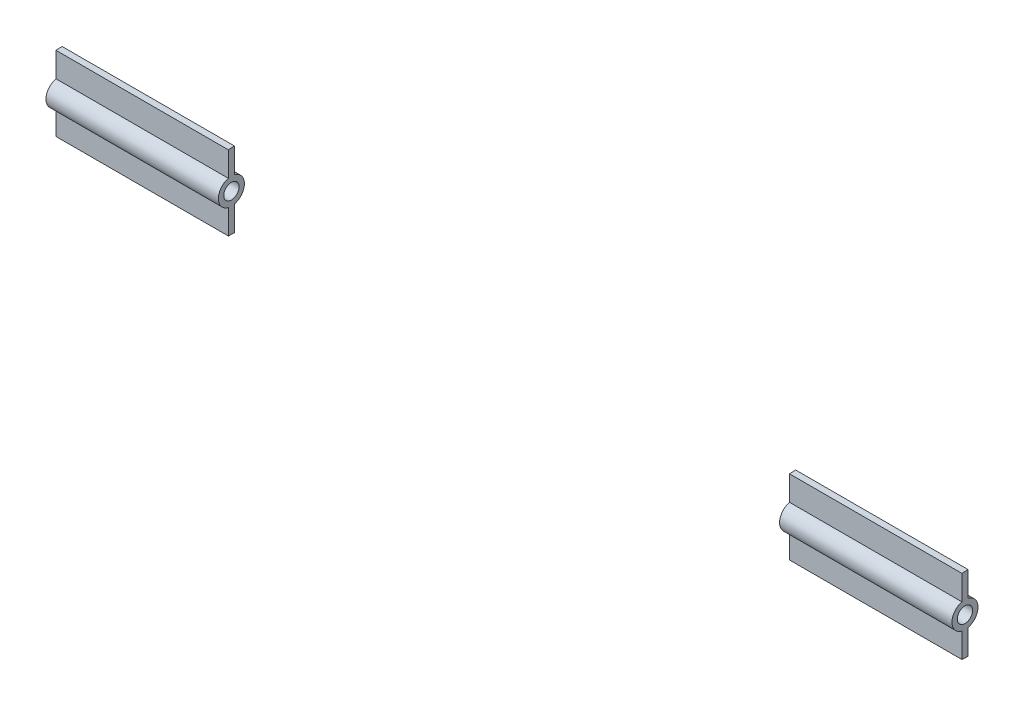
SolidWorks part; units mm, degrees
material "ABS"
ref_plane "Front Plane" through (0, 0, 0) normal (0, 0, 1) x (1, 0, 0)
ref_plane "Top Plane" through (0, 0, 0) normal (0, 1, 0) x (1, 0, 0)
ref_plane "Right Plane" through (0, 0, 0) normal (1, 0, 0) x (0, 0, -1)
body saved out of another part "Stock-V-tail-1" rebuild error yes
ref_plane "Plane1" through (237.5, 0, 0) normal (-1, 0, 0) x (0, 0, 1)
sketch "Sketch1" plane through (237.5, 0, 0) normal (-1, 0, 0) x (0, 0, 1)
  arc A1 (136.0381, 9.253) -> (136.0381, -9.253) centre (141.8338, 0) ccw
  arc A2 (136.0381, 9.253) -> (136.0381, -9.253) centre (141.8338, 0) ccw
  circle A5 centre (62, 0) radius 9 construction
  circle A6 centre (62, 0) radius 9
  spline S0 degree 3 poles (1848.5448, -5455.4948) (1254.8548, 370.5463) (691.9533, 13.7835) (107.9109, -10.5652) (94.6227, -10.9527) (84.1989, -11.1308) (76.6156, -11.194) (69.2347, -11.1852) (62.0877, -11.0901) (55.2058, -10.9234) (48.6191, -10.6715) (42.3552, -10.3437) (36.4402, -9.9323) (30.8991, -9.4444) (25.7573, -8.8756) (21.0365, -8.2367) (16.7549, -7.5443) (12.9305, -6.8014) (9.5757, -6.0106) (6.7064, -5.1453) (4.3287, -4.1895) (2.4645, -3.1349) (1.1239, -2.0336) (0.2866, -1.0243) (-0.1173, 0) (0.2866, 1.0243) (1.1239, 2.0336) (2.4645, 3.1349) (4.3287, 4.1895) (6.7064, 5.1453) (9.5757, 6.0106) (12.9305, 6.8014) (16.7549, 7.5443) (21.0365, 8.2367) (25.7573, 8.8756) (30.8991, 9.4444) (36.4402, 9.9323) (42.3552, 10.3437) (48.6191, 10.6715) (55.2058, 10.9234) (62.0877, 11.0901) (69.2347, 11.1852) (76.6156, 11.194) (84.1989, 11.1308) (94.6227, 10.9527) (107.9109, 10.5652) (691.9613, -13.7839) (1254.8704, -370.5562) (1848.5696, 5455.7381) knots -6.166881 -6.166881 -6.166881 -6.166881 0.043484 0.10192 0.159336 0.187352 0.214748 0.241409 0.267232 0.292102 0.315909 0.338567 0.359984 0.380076 0.398764 0.415965 0.431629 0.445697 0.45812 0.468916 0.478106 0.485795 0.492019 0.496734 0.5 0.503266 0.507981 0.514205 0.521894 0.531084 0.54188 0.554303 0.568371 0.584035 0.601236 0.619924 0.640016 0.661433 0.684091 0.707898 0.732768 0.758591 0.785252 0.812648 0.840664 0.89808 0.956516 7.166968 7.166968 7.166968 7.166968 only from (136.0381, -9.253) to (136.0381, 9.253)
  spline S1 degree 3 poles (136.0381, -9.253) (132.0261, -9.4717) (122.621, -9.9519) (107.9109, -10.5652) (94.6227, -10.9527) (84.1989, -11.1308) (76.6156, -11.194) (69.2347, -11.1852) (62.0877, -11.0901) (55.2058, -10.9234) (48.6191, -10.6715) (42.3552, -10.3437) (36.4402, -9.9323) (30.8991, -9.4444) (25.7573, -8.8756) (21.0365, -8.2367) (16.7549, -7.5443) (12.9305, -6.8014) (9.5757, -6.0106) (6.7064, -5.1453) (4.3287, -4.1895) (2.4645, -3.1349) (1.1239, -2.0336) (0.2866, -1.0243) (-0.1173, 0) (0.2866, 1.0243) (1.1239, 2.0336) (2.4645, 3.1349) (4.3287, 4.1895) (6.7064, 5.1453) (9.5757, 6.0106) (12.9305, 6.8014) (16.7549, 7.5443) (21.0365, 8.2367) (25.7573, 8.8756) (30.8991, 9.4444) (36.4402, 9.9323) (42.3552, 10.3437) (48.6191, 10.6715) (55.2058, 10.9234) (62.0877, 11.0901) (69.2347, 11.1852) (76.6156, 11.194) (84.1989, 11.1308) (94.6227, 10.9527) (107.9109, 10.5652) (122.621, 9.9519) (132.0261, 9.4717) (136.0381, 9.253) knots 0 0 0 0 0.043484 0.10192 0.159336 0.187352 0.214748 0.241409 0.267232 0.292102 0.315909 0.338567 0.359984 0.380076 0.398764 0.415965 0.431629 0.445697 0.45812 0.468916 0.478106 0.485795 0.492019 0.496734 0.5 0.503266 0.507981 0.514205 0.521894 0.531084 0.54188 0.554303 0.568371 0.584035 0.601236 0.619924 0.640016 0.661433 0.684091 0.707898 0.732768 0.758591 0.785252 0.812648 0.840664 0.89808 0.956516 1 1 1 1
extrude "Boss-Extrude1" add sketch "Sketch1" along normal up to surface (1 mm away) rebuild error yes
sketch "Sketch3" plane through (236.5, 0, 0) normal (-1, 0, 0) x (0, 0, 1)
  line L0 (62, 0) -> (117, 0) construction
  line L1 (116.2, 9.8114) -> (116.2, 3.3045)
  line L2 (117.8, 9.7438) -> (117.8, 3.3045)
  line L3 (117, 9.7778) -> (117, -9.7778) construction
  line L4 (116.2, -9.8114) -> (116.2, -3.3045)
  line L5 (117.8, -9.7438) -> (117.8, -3.3045)
  line L6 (116.2, 9.8114) -> (117.8, 9.7438)
  line L7 (116.2, -9.8114) -> (117.8, -9.7438)
  circle A0 centre (62, 0) radius 9 construction
  circle A1 centre (62, 0) radius 9 construction
  circle A2 centre (117, 0) radius 2
  arc A3 (116.2, 3.3045) -> (116.2, -3.3045) centre (117, 0) ccw
  arc A4 (117.8, -3.3045) -> (117.8, 3.3045) centre (117, 0) ccw
  spline S0 degree 3 poles (1848.5448, 5455.4948) (1254.8548, -370.5463) (691.9533, -13.7835) (107.9109, 10.5652) (94.6227, 10.9527) (84.1989, 11.1308) (76.6156, 11.194) (69.2347, 11.1852) (62.0877, 11.0901) (55.2058, 10.9234) (48.6191, 10.6715) (42.3552, 10.3437) (36.4402, 9.9323) (30.8991, 9.4444) (25.7573, 8.8756) (21.0365, 8.2367) (16.7549, 7.5443) (12.9305, 6.8014) (9.5757, 6.0106) (6.7064, 5.1453) (4.3287, 4.1895) (2.4645, 3.1349) (1.1239, 2.0336) (0.2866, 1.0243) (-0.1173, 0) (0.2866, -1.0243) (1.1239, -2.0336) (2.4645, -3.1349) (4.3287, -4.1895) (6.7064, -5.1453) (9.5757, -6.0106) (12.9305, -6.8014) (16.7549, -7.5443) (21.0365, -8.2367) (25.7573, -8.8756) (30.8991, -9.4444) (36.4402, -9.9323) (42.3552, -10.3437) (48.6191, -10.6715) (55.2058, -10.9234) (62.0877, -11.0901) (69.2347, -11.1852) (76.6156, -11.194) (84.1989, -11.1308) (94.6227, -10.9527) (107.9109, -10.5652) (691.9613, 13.7839) (1254.8704, 370.5562) (1848.5696, -5455.7381) knots -6.166881 -6.166881 -6.166881 -6.166881 0.043484 0.10192 0.159336 0.187352 0.214748 0.241409 0.267232 0.292102 0.315909 0.338567 0.359984 0.380076 0.398764 0.415965 0.431629 0.445697 0.45812 0.468916 0.478106 0.485795 0.492019 0.496734 0.5 0.503266 0.507981 0.514205 0.521894 0.531084 0.54188 0.554303 0.568371 0.584035 0.601236 0.619924 0.640016 0.661433 0.684091 0.707898 0.732768 0.758591 0.785252 0.812648 0.840664 0.89808 0.956516 7.166968 7.166968 7.166968 7.166968 only from (136.0381, 9.253) to (136.0381, -9.253)
  spline S1 degree 3 poles (136.0381, 9.253) (132.0261, 9.4717) (122.621, 9.9519) (107.9109, 10.5652) (94.6227, 10.9527) (84.1989, 11.1308) (76.6156, 11.194) (69.2347, 11.1852) (62.0877, 11.0901) (55.2058, 10.9234) (48.6191, 10.6715) (42.3552, 10.3437) (36.4402, 9.9323) (30.8991, 9.4444) (25.7573, 8.8756) (21.0365, 8.2367) (16.7549, 7.5443) (12.9305, 6.8014) (9.5757, 6.0106) (6.7064, 5.1453) (4.3287, 4.1895) (2.4645, 3.1349) (1.1239, 2.0336) (0.2866, 1.0243) (-0.1173, 0) (0.2866, -1.0243) (1.1239, -2.0336) (2.4645, -3.1349) (4.3287, -4.1895) (6.7064, -5.1453) (9.5757, -6.0106) (12.9305, -6.8014) (16.7549, -7.5443) (21.0365, -8.2367) (25.7573, -8.8756) (30.8991, -9.4444) (36.4402, -9.9323) (42.3552, -10.3437) (48.6191, -10.6715) (55.2058, -10.9234) (62.0877, -11.0901) (69.2347, -11.1852) (76.6156, -11.194) (84.1989, -11.1308) (94.6227, -10.9527) (107.9109, -10.5652) (122.621, -9.9519) (132.0261, -9.4717) (136.0381, -9.253) knots 0 0 0 0 0.043484 0.10192 0.159336 0.187352 0.214748 0.241409 0.267232 0.292102 0.315909 0.338567 0.359984 0.380076 0.398764 0.415965 0.431629 0.445697 0.45812 0.468916 0.478106 0.485795 0.492019 0.496734 0.5 0.503266 0.507981 0.514205 0.521894 0.531084 0.54188 0.554303 0.568371 0.584035 0.601236 0.619924 0.640016 0.661433 0.684091 0.707898 0.732768 0.758591 0.785252 0.812648 0.840664 0.89808 0.956516 1 1 1 1 construction
  spline S2 degree 1 poles (136.0163, 8.8536) (136.0163, -8.8536) knots 0 0 1 1 construction
  spline S3 degree 3 poles (136.0163, 8.8536) (130.2514, 9.1678) (124.2459, 9.4651) (118.1056, 9.7307) (117.6666, 9.7495) (117.4, 9.7609) (117.1333, 9.7722) (116.8666, 9.7835) (116.6, 9.7947) (116.3333, 9.8058) (111.2706, 10.0168) (100.5041, 10.4086) (84.0958, 10.7773) (69.6656, 10.8196) (58.1244, 10.6127) (49.4737, 10.3215) (40.8313, 9.8647) (33.6424, 9.3078) (27.907, 8.7199) (23.6162, 8.1931) (19.3389, 7.5713) (15.0835, 6.8329) (11.5652, 6.0893) (8.7915, 5.3615) (6.7466, 4.7182) (4.7593, 3.9358) (2.8953, 2.9508) (1.5069, 1.8551) (0.7638, 0.969) (0.4573, 0.3737) (0.3714, 0) (0.4573, -0.3737) (0.7638, -0.969) (1.5069, -1.8551) (2.8953, -2.9508) (4.7593, -3.9358) (6.7466, -4.7182) (8.7915, -5.3615) (11.5652, -6.0893) (15.0835, -6.8329) (19.3389, -7.5713) (23.6162, -8.1931) (27.907, -8.7199) (33.6424, -9.3078) (40.8313, -9.8647) (49.4737, -10.3215) (58.1244, -10.6127) (69.6656, -10.8196) (84.0958, -10.7773) (100.5041, -10.4086) (111.2706, -10.0168) (116.3333, -9.8058) (116.6, -9.7947) (116.8666, -9.7835) (117.1333, -9.7722) (117.4, -9.7609) (117.6666, -9.7495) (118.1056, -9.7307) (124.2459, -9.4651) (130.2514, -9.1678) (136.0163, -8.8536) knots 0 0 0 0 0.0625 0.065089 0.066534 0.067256 0.067979 0.069423 0.070146 0.070868 0.072313 0.125 0.1875 0.25 0.28125 0.3125 0.34375 0.375 0.390625 0.40625 0.421875 0.4375 0.453125 0.460938 0.46875 0.476562 0.484375 0.492188 0.496094 0.498047 0.5 0.501953 0.503906 0.507812 0.515625 0.523438 0.53125 0.539062 0.546875 0.5625 0.578125 0.59375 0.609375 0.625 0.65625 0.6875 0.71875 0.75 0.8125 0.875 0.927687 0.929132 0.929854 0.930577 0.932021 0.932744 0.933466 0.934911 0.9375 1 1 1 1 construction
  dimension "D1" = 0.4
  dimension "D2" = 55
  dimension "D3" = 4
  dimension "D4" = 6.8
  dimension "D5" = 0.8
  dimension "D6" = 0.8
extrude "Cut-Extrude1" cut sketch "Sketch3" against normal blind 44 contours A2 rebuild error yes
extrude "Boss-Extrude2" add sketch "Sketch3<3>" against normal blind 45 contours L5 A4 L2 L6 L1 A3 L4 L7 A2 region at (236.5, 9.5701, 116.9912)
sketch "Sketch3<3>" plane through (236.5, 0, 0) normal (-1, 0, 0) x (0, 0, 1) same geometry as "Sketch3"
sketch "Sketch4" plane through (473, 0, 0) normal (1, 0, 0) x (0, 0, -1)
  line L0 (-117, 9.7778) -> (-117, -9.7778) construction
  line L1 (-117.8, 9.7438) -> (-117.8, 3.3045)
  line L2 (-116.2, 9.8114) -> (-116.2, 3.3045)
  line L3 (-117.8, -9.7438) -> (-117.8, -3.3045)
  line L4 (-116.2, -9.8114) -> (-116.2, -3.3045)
  line L5 (-117.8, -9.7438) -> (-116.2, -9.8114)
  line L6 (-117.8, 9.7438) -> (-116.2, 9.8114)
  circle A0 centre (-62, 0) radius 9 construction
  circle A1 centre (-62, 0) radius 9 construction
  circle A2 centre (-117, 0) radius 2
  arc A3 (-117.8, 3.3045) -> (-117.8, -3.3045) centre (-117, 0) ccw
  arc A4 (-116.2, -3.3045) -> (-116.2, 3.3045) centre (-117, 0) ccw
  spline S0 degree 3 poles (-1848.5448, -5455.4948) (-1254.8548, 370.5463) (-691.9533, 13.7835) (-107.9109, -10.5652) (-94.6227, -10.9527) (-84.1989, -11.1308) (-76.6156, -11.194) (-69.2347, -11.1852) (-62.0877, -11.0901) (-55.2058, -10.9234) (-48.6191, -10.6715) (-42.3552, -10.3437) (-36.4402, -9.9323) (-30.8991, -9.4444) (-25.7573, -8.8756) (-21.0365, -8.2367) (-16.7549, -7.5443) (-12.9305, -6.8014) (-9.5757, -6.0106) (-6.7064, -5.1453) (-4.3287, -4.1895) (-2.4645, -3.1349) (-1.1239, -2.0336) (-0.2866, -1.0243) (0.1173, 0) (-0.2866, 1.0243) (-1.1239, 2.0336) (-2.4645, 3.1349) (-4.3287, 4.1895) (-6.7064, 5.1453) (-9.5757, 6.0106) (-12.9305, 6.8014) (-16.7549, 7.5443) (-21.0365, 8.2367) (-25.7573, 8.8756) (-30.8991, 9.4444) (-36.4402, 9.9323) (-42.3552, 10.3437) (-48.6191, 10.6715) (-55.2058, 10.9234) (-62.0877, 11.0901) (-69.2347, 11.1852) (-76.6156, 11.194) (-84.1989, 11.1308) (-94.6227, 10.9527) (-107.9109, 10.5652) (-691.9613, -13.7839) (-1254.8704, -370.5562) (-1848.5696, 5455.7381) knots -6.166881 -6.166881 -6.166881 -6.166881 0.043484 0.10192 0.159336 0.187352 0.214748 0.241409 0.267232 0.292102 0.315909 0.338567 0.359984 0.380076 0.398764 0.415965 0.431629 0.445697 0.45812 0.468916 0.478106 0.485795 0.492019 0.496734 0.5 0.503266 0.507981 0.514205 0.521894 0.531084 0.54188 0.554303 0.568371 0.584035 0.601236 0.619924 0.640016 0.661433 0.684091 0.707898 0.732768 0.758591 0.785252 0.812648 0.840664 0.89808 0.956516 7.166968 7.166968 7.166968 7.166968 only from (-136.0381, -9.253) to (-136.0381, 9.253)
  spline S1 degree 3 poles (-136.0381, -9.253) (-132.0261, -9.4717) (-122.621, -9.9519) (-107.9109, -10.5652) (-94.6227, -10.9527) (-84.1989, -11.1308) (-76.6156, -11.194) (-69.2347, -11.1852) (-62.0877, -11.0901) (-55.2058, -10.9234) (-48.6191, -10.6715) (-42.3552, -10.3437) (-36.4402, -9.9323) (-30.8991, -9.4444) (-25.7573, -8.8756) (-21.0365, -8.2367) (-16.7549, -7.5443) (-12.9305, -6.8014) (-9.5757, -6.0106) (-6.7064, -5.1453) (-4.3287, -4.1895) (-2.4645, -3.1349) (-1.1239, -2.0336) (-0.2866, -1.0243) (0.1173, 0) (-0.2866, 1.0243) (-1.1239, 2.0336) (-2.4645, 3.1349) (-4.3287, 4.1895) (-6.7064, 5.1453) (-9.5757, 6.0106) (-12.9305, 6.8014) (-16.7549, 7.5443) (-21.0365, 8.2367) (-25.7573, 8.8756) (-30.8991, 9.4444) (-36.4402, 9.9323) (-42.3552, 10.3437) (-48.6191, 10.6715) (-55.2058, 10.9234) (-62.0877, 11.0901) (-69.2347, 11.1852) (-76.6156, 11.194) (-84.1989, 11.1308) (-94.6227, 10.9527) (-107.9109, 10.5652) (-122.621, 9.9519) (-132.0261, 9.4717) (-136.0381, 9.253) knots 0 0 0 0 0.043484 0.10192 0.159336 0.187352 0.214748 0.241409 0.267232 0.292102 0.315909 0.338567 0.359984 0.380076 0.398764 0.415965 0.431629 0.445697 0.45812 0.468916 0.478106 0.485795 0.492019 0.496734 0.5 0.503266 0.507981 0.514205 0.521894 0.531084 0.54188 0.554303 0.568371 0.584035 0.601236 0.619924 0.640016 0.661433 0.684091 0.707898 0.732768 0.758591 0.785252 0.812648 0.840664 0.89808 0.956516 1 1 1 1 construction
  spline S2 degree 1 poles (-136.0163, -8.8536) (-136.0163, 8.8536) knots 0 0 1 1 construction
  spline S3 degree 3 poles (-136.0163, -8.8536) (-130.2514, -9.1678) (-124.2459, -9.4651) (-118.1056, -9.7307) (-117.6666, -9.7495) (-117.4, -9.7609) (-117.1333, -9.7722) (-116.8666, -9.7835) (-116.6, -9.7947) (-116.3333, -9.8058) (-111.2706, -10.0168) (-100.5041, -10.4086) (-84.0958, -10.7773) (-69.6656, -10.8196) (-58.1244, -10.6127) (-49.4737, -10.3215) (-40.8313, -9.8647) (-33.6424, -9.3078) (-27.907, -8.7199) (-23.6162, -8.1931) (-19.3389, -7.5713) (-15.0835, -6.8329) (-11.5652, -6.0893) (-8.7915, -5.3615) (-6.7466, -4.7182) (-4.7593, -3.9358) (-2.8953, -2.9508) (-1.5069, -1.8551) (-0.7638, -0.969) (-0.4573, -0.3737) (-0.3714, 0) (-0.4573, 0.3737) (-0.7638, 0.969) (-1.5069, 1.8551) (-2.8953, 2.9508) (-4.7593, 3.9358) (-6.7466, 4.7182) (-8.7915, 5.3615) (-11.5652, 6.0893) (-15.0835, 6.8329) (-19.3389, 7.5713) (-23.6162, 8.1931) (-27.907, 8.7199) (-33.6424, 9.3078) (-40.8313, 9.8647) (-49.4737, 10.3215) (-58.1244, 10.6127) (-69.6656, 10.8196) (-84.0958, 10.7773) (-100.5041, 10.4086) (-111.2706, 10.0168) (-116.3333, 9.8058) (-116.6, 9.7947) (-116.8666, 9.7835) (-117.1333, 9.7722) (-117.4, 9.7609) (-117.6666, 9.7495) (-118.1056, 9.7307) (-124.2459, 9.4651) (-130.2514, 9.1678) (-136.0163, 8.8536) knots 0 0 0 0 0.0625 0.065089 0.066534 0.067256 0.067979 0.069423 0.070146 0.070868 0.072313 0.125 0.1875 0.25 0.28125 0.3125 0.34375 0.375 0.390625 0.40625 0.421875 0.4375 0.453125 0.460938 0.46875 0.476562 0.484375 0.492188 0.496094 0.498047 0.5 0.501953 0.503906 0.507812 0.515625 0.523438 0.53125 0.539062 0.546875 0.5625 0.578125 0.59375 0.609375 0.625 0.65625 0.6875 0.71875 0.75 0.8125 0.875 0.927687 0.929132 0.929854 0.930577 0.932021 0.932744 0.933466 0.934911 0.9375 1 1 1 1 construction
  dimension "D2" = 4
  dimension "D1" = 0.4
extrude "Cut-Extrude2" cut sketch "Sketch4" against normal blind 44 contours A2 rebuild error yes
extrude "Boss-Extrude3" add sketch "Sketch4<3>" against normal blind 45 contours L4 A4 L2 L6 L1 A3 L3 L5 A2 region at (473, 9.5701, 116.9912)
sketch "Sketch4<3>" plane through (473, 0, 0) normal (1, 0, 0) x (0, 0, -1) same geometry as "Sketch4"
